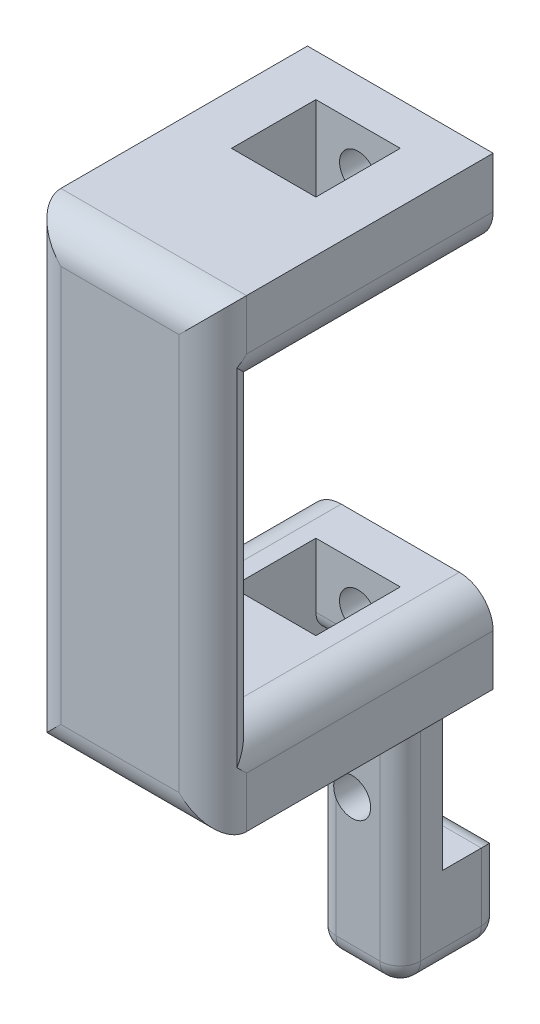
SolidWorks part; units mm, degrees
ref_plane "Płaszczyzna przednia" through (0, 0, 0) normal (0, 0, 1) x (1, 0, 0)
ref_plane "Płaszczyzna górna" through (0, 0, 0) normal (0, 1, 0) x (1, 0, 0)
ref_plane "Płaszczyzna prawa" through (0, 0, 0) normal (1, 0, 0) x (0, 0, -1)
sketch "Szkic1" plane through (0, 0, 158.8329) normal (0, 0, 1) x (1, 0, 0)
  line L0 (-31.9233, -22.4743) -> (2.0767, -22.4743) construction
  line L1 (-19.2684, -17.4743) -> (-8.2684, -17.4743)
  line L2 (-19.2684, -17.4743) -> (-19.2684, -22.4743)
  line L3 (-19.2684, -22.4743) -> (-8.2684, -22.4743)
  line L4 (-8.2684, -17.4743) -> (-8.2684, -22.4743)
  line L5 (-19.2684, -17.4743) -> (-8.2684, -22.4743) construction
  line L6 (-19.2684, -22.4743) -> (-8.2684, -17.4743) construction
  line L14 (-19.2684, 0.0257) -> (-8.2684, 0.0257)
  line L15 (-19.2684, 0.0257) -> (-19.2684, 5.0257)
  line L16 (-19.2684, 5.0257) -> (-8.2684, 5.0257)
  line L17 (-8.2684, 0.0257) -> (-8.2684, 5.0257)
  line L18 (-19.2684, 0.0257) -> (-8.2684, 5.0257) construction
  line L19 (-19.2684, 5.0257) -> (-8.2684, 0.0257) construction
  circle A4 centre (-13.7684, -19.9743) radius 1.1
  circle A5 centre (-13.7684, 2.5257) radius 1.1
  dimension "D4" = 2.2
  dimension "D14" = 2.2
  dimension "D1" = 22.5
  dimension "D3" = 2.5
  dimension "D7" = 2.5
  dimension "D8" = 5.5
  dimension "D15" = 5.5
extrude "Dodanie-wyciągnięcie1" add sketch "Szkic1" along normal blind 2.5
sketch "Sketch1" plane through (0, 0, 161.3329) normal (0, 0, 1) x (1, 0, 0)
  line L0 (-19.2684, -22.4743) -> (-8.2684, -22.4743) construction
  line L1 (-19.2684, -17.4743) -> (-16.2684, -17.4743)
  line L2 (-19.2684, -17.4743) -> (-19.2684, -22.4743)
  line L3 (-19.2684, -22.4743) -> (-16.2684, -22.4743)
  line L4 (-16.2684, -17.4743) -> (-16.2684, -22.4743)
  line L5 (-8.2684, 5.0257) -> (-19.2684, 5.0257) construction
  line L6 (-19.2684, 0.0257) -> (-16.2684, 0.0257)
  line L7 (-19.2684, 0.0257) -> (-19.2684, 5.0257)
  line L8 (-19.2684, 5.0257) -> (-16.2684, 5.0257)
  line L9 (-16.2684, 0.0257) -> (-16.2684, 5.0257)
  line L10 (-19.2684, 0.0257) -> (-8.2684, 0.0257) construction
  line L11 (-8.2684, 5.0257) -> (-11.2684, 5.0257)
  line L12 (-8.2684, 5.0257) -> (-8.2684, 0.0257)
  line L13 (-8.2684, 0.0257) -> (-11.2684, 0.0257)
  line L14 (-11.2684, 5.0257) -> (-11.2684, 0.0257)
  line L16 (-8.2684, -17.4743) -> (-11.2684, -17.4743)
  line L17 (-8.2684, -17.4743) -> (-8.2684, -22.4743)
  line L18 (-8.2684, -22.4743) -> (-11.2684, -22.4743)
  line L19 (-11.2684, -17.4743) -> (-11.2684, -22.4743)
  dimension "D1" = 3
  dimension "D2" = 3
extrude "Boss-Extrude1" add sketch "Sketch1" along normal blind 5
sketch "Sketch2" plane through (0, 0, 166.3329) normal (0, 0, 1) x (1, 0, 0)
  line L1 (-19.2684, -22.4743) -> (-8.2684, -22.4743)
  line L2 (-19.2684, -22.4743) -> (-19.2684, -17.4743)
  line L3 (-19.2684, -17.4743) -> (-8.2684, -17.4743)
  line L4 (-8.2684, -22.4743) -> (-8.2684, -17.4743)
  line L5 (-19.2684, 0.0257) -> (-8.2684, 0.0257)
  line L6 (-19.2684, 0.0257) -> (-19.2684, 5.0257)
  line L7 (-19.2684, 5.0257) -> (-8.2684, 5.0257)
  line L8 (-8.2684, 0.0257) -> (-8.2684, 5.0257)
extrude "Boss-Extrude2" add sketch "Sketch2" along normal blind 6.11
sketch "Sketch3" plane through (0, 0, 172.4429) normal (0, 0, 1) x (1, 0, 0)
  line L1 (-19.2684, -22.4743) -> (-8.2684, -22.4743)
  line L2 (-19.2684, -22.4743) -> (-19.2684, 5.0257)
  line L3 (-19.2684, 5.0257) -> (-8.2684, 5.0257)
  line L4 (-8.2684, -22.4743) -> (-8.2684, 5.0257)
extrude "Boss-Extrude3" add sketch "Sketch3" along normal blind 3
fillet "Fillet1" radius 2 4 edges at (-13.7684, 5.0257, 175.4429) (-8.2684, -8.7243, 175.4429) (-13.7684, -22.4743, 175.4429) (-19.2684, -8.7243, 175.4429)
fillet "Fillet4" radius 2 6 edges at (-19.2684, -8.7243, 172.4429) (-8.2684, -8.7243, 172.4429) (-19.2684, -17.4743, 165.6379) (-8.2684, -17.4743, 165.6379) (-19.2684, 0.0257, 165.6379) (-8.2684, 0.0257, 165.6379)
sketch "Sketch4" plane through (0, -22.4743, 0) normal (0, -1, 0) x (1, 0, 0)
  line L0 (-19.2684, 158.8329) -> (-8.2684, 158.8329) construction
  line L1 (-11.2684, 161.3329) -> (-16.2684, 161.3329)
  line L2 (-11.2684, 161.3329) -> (-11.2684, 158.8329)
  line L3 (-11.2684, 158.8329) -> (-16.2684, 158.8329)
  line L4 (-16.2684, 161.3329) -> (-16.2684, 158.8329)
extrude "Boss-Extrude4" add sketch "Sketch4" along normal blind 16
sketch "Sketch5" plane through (0, 0, 158.8329) normal (0, 0, -1) x (-1, 0, 0)
  line L0 (16.2684, -38.4743) -> (16.2684, -22.4743) construction
  line L1 (11.2684, -38.4743) -> (16.2684, -38.4743)
  line L2 (11.2684, -38.4743) -> (11.2684, -33.27)
  line L3 (11.2684, -33.27) -> (16.2684, -33.27)
  line L4 (16.2684, -38.4743) -> (16.2684, -33.27)
extrude "Boss-Extrude5" add sketch "Sketch5" along normal blind 3.5
sketch "Sketch6" plane through (0, 0, 158.8329) normal (0, 0, -1) x (-1, 0, 0)
  circle A0 centre (14.1236, -29.6723) radius 1.1 construction
  circle A1 centre (14.1236, -29.6723) radius 1.1
extrude "Cut-Extrude1" cut sketch "Sketch6" against normal up to next
fillet "Fillet5" radius 1.2 4 edges at (-13.7684, -38.4743, 155.3329) (-11.2684, -35.8721, 155.3329) (-13.7684, -33.27, 155.3329) (-16.2684, -35.8721, 155.3329)
fillet "Fillet6" radius 1.2 7 edges at (-11.6199, -38.1228, 155.6844) (-15.9169, -38.1228, 155.6844) (-11.2684, -38.4743, 158.9329) (-16.2684, -38.4743, 158.9329) (-13.7684, -38.4743, 161.3329) (-11.2684, -30.4743, 161.3329) (-16.2684, -30.4743, 161.3329)
fillet "Fillet7" radius 1.2 2 edges at (-15.6684, -22.4743, 161.3329) (-11.8684, -22.4743, 161.3329)
